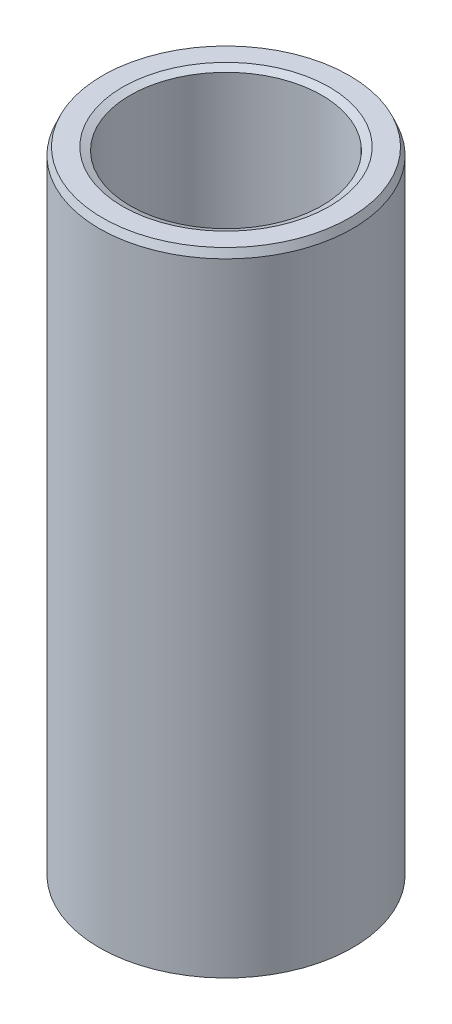
SolidWorks part; units mm, degrees
ref_plane "Front Plane" through (0, 0, 0) normal (0, 0, 1) x (1, 0, 0)
ref_plane "Top Plane" through (0, 0, 0) normal (0, 1, 0) x (1, 0, 0)
ref_plane "Right Plane" through (0, 0, 0) normal (1, 0, 0) x (0, 0, -1)
sketch "Sketch1" plane through (0, 0, 0) normal (0, 1, 0) x (1, 0, 0)
  circle A0 centre (0, 0) radius 55
  dimension "SLEEVE_OD" = 110
extrude "Boss-Extrude1" add sketch "Sketch1" along normal blind 275.1415
sketch "Sketch2" plane through (0, 0, 0) normal (0, 1, 0) x (1, 0, 0)
  circle A0 centre (0, 0) radius 41.6128
  dimension "BORE_D" = 83.2255
extrude "Cut-Extrude1" cut sketch "Sketch2" along normal through all
chamfer "Chamfer1" distance 3.292 angle 23.144 4 edges at (0, 275.1415, 41.6128) (0, 0, 41.6128) (0, 0, 55) (0, 275.1415, 55) first distance on face at (0, 275.1415, 41.6128) first distance on face at (0, 0, 41.6128) first distance on face at (0, 275.1415, 55)
